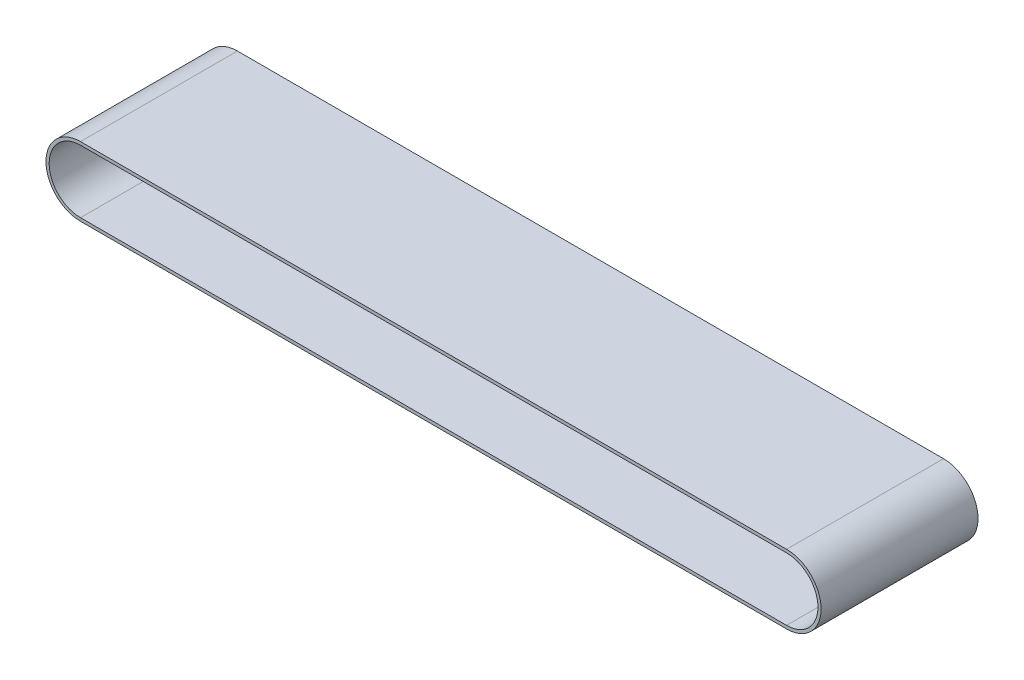
SolidWorks part; units mm, degrees
ref_plane "Front Plane" through (0, 0, 0) normal (0, 0, 1) x (1, 0, 0)
ref_plane "Top Plane" through (0, 0, 0) normal (0, 1, 0) x (1, 0, 0)
ref_plane "Right Plane" through (0, 0, 0) normal (1, 0, 0) x (0, 0, -1)
sketch "Sketch1" plane through (0, 0, 0) normal (0, 0, 1) x (1, 0, 0)
  line L0 (-371.3468, 20) -> (78.6532, 20)
  line L1 (78.6532, -24) -> (-371.3468, -24)
  arc A0 (-371.3468, 20) -> (-371.3468, -24) centre (-371.3468, -2) ccw
  arc A1 (78.6532, -24) -> (78.6532, 20) centre (78.6532, -2) ccw
  dimension "D1" = 44
  dimension "D2" = 44
  dimension "D3" = 450
extrude "Boss-Extrude1" add sketch "Sketch1" along normal blind 100
shell "Shell2" thickness 2 removed face at (-146.3468, -2, 0) removed face at (-146.3468, -2, 100)
